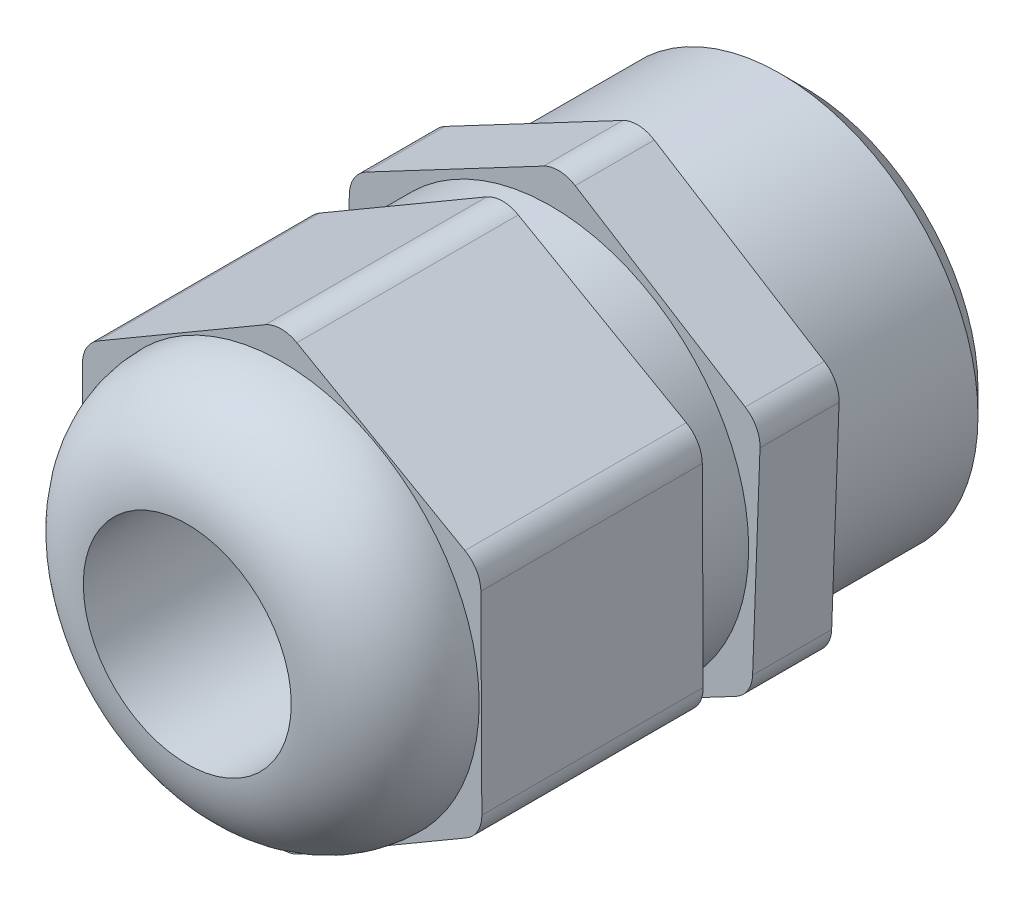
SolidWorks part; units mm, degrees
material "Резина"
ref_plane "Спереди" through (0, 0, 0) normal (0, 0, 1) x (1, 0, 0)
ref_plane "Сверху" through (0, 0, 0) normal (0, 1, 0) x (1, 0, 0)
ref_plane "Справа" through (0, 0, 0) normal (1, 0, 0) x (0, 0, -1)
sketch "Эскиз2" plane through (0, 0, 0) normal (0, 0, 1) x (1, 0, 0)
  line L1 (12.7048, -7.9743) -> (13.2583, 7.0155)
  line L2 (13.2583, 7.0155) -> (0.5535, 14.9898)
  line L3 (0.5535, 14.9898) -> (-12.7048, 7.9743)
  line L4 (-12.7048, 7.9743) -> (-13.2583, -7.0155)
  line L5 (-13.2583, -7.0155) -> (-0.5535, -14.9898)
  line L6 (-0.5535, -14.9898) -> (12.7048, -7.9743)
  circle A0 centre (0, 0) radius 15 construction
extrude "Бобышка-Вытянуть1" add sketch "Эскиз2" along normal blind 5
sketch "Эскиз3" plane through (0, 0, 0) normal (0, 0, -1) x (-1, 0, 0)
  circle A0 centre (0, 0) radius 12.5
  dimension "D1" = 25
extrude "Бобышка-Вытянуть2" add sketch "Эскиз3" along normal blind 11
chamfer "Фаска1" distance 1.5 angle 45 1 edges at (-12.5, 0, -11)
sketch "Эскиз4" plane through (0, 0, 5) normal (0, 0, 1) x (1, 0, 0)
  circle A0 centre (0, 0) radius 12.5
  dimension "D1" = 25
extrude "Бобышка-Вытянуть3" add sketch "Эскиз4" along normal blind 3
sketch "Эскиз5" plane through (0, 0, 8) normal (0, 0, 1) x (1, 0, 0)
  line L1 (12.5594, 7.3355) -> (-0.0731, 14.5445)
  line L2 (-0.0731, 14.5445) -> (-12.6325, 7.209)
  line L3 (-12.6325, 7.209) -> (-12.5594, -7.3355)
  line L4 (-12.5594, -7.3355) -> (0.0731, -14.5445)
  line L5 (0.0731, -14.5445) -> (12.6325, -7.209)
  line L6 (12.6325, -7.209) -> (12.5594, 7.3355)
  circle A0 centre (0, 0) radius 12.5961 construction
extrude "Бобышка-Вытянуть4" add sketch "Эскиз5" along normal blind 14
sketch "Эскиз6" plane through (0, 0, 22) normal (0, 0, 1) x (1, 0, 0)
  circle A0 centre (0, 0) radius 12.459
extrude "Бобышка-Вытянуть5" add sketch "Эскиз6" along normal blind 6
fillet "Скругление1" radius 6 1 edges at (12.459, 0, 28)
sketch "Эскиз7" plane through (0, 0, 28) normal (0, 0, 1) x (1, 0, 0)
  circle A0 centre (0, 0) radius 6.5742
extrude "Вырез-Вытянуть1" cut sketch "Эскиз7" against normal blind 42
fillet "Скругление2" radius 2 12 edges at (-12.5594, -7.3355, 15) (-12.6325, 7.209, 15) (0.0731, -14.5445, 15) (12.6325, -7.209, 15) (-0.0731, 14.5445, 15) (12.5594, 7.3355, 15) (0.5535, 14.9898, 2.5) (13.2583, 7.0155, 2.5) (12.7048, -7.9743, 2.5) (-0.5535, -14.9898, 2.5) (-12.7048, 7.9743, 2.5) (-13.2583, -7.0155, 2.5)
